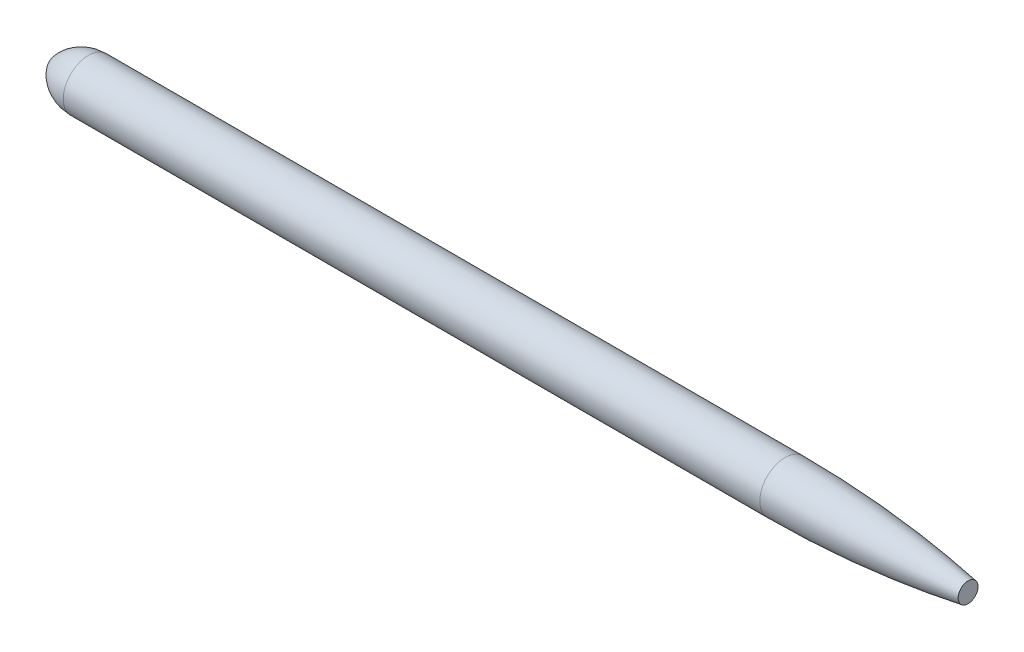
SolidWorks part; units mm, degrees
ref_plane "Front Plane" through (0, 0, 0) normal (0, 0, 1) x (1, 0, 0)
ref_plane "Top Plane" through (0, 0, 0) normal (0, 1, 0) x (1, 0, 0)
ref_plane "Right Plane" through (0, 0, 0) normal (1, 0, 0) x (0, 0, -1)
sketch "rootSketch" plane through (0, 0, 0) normal (0, 1, 0) x (1, 0, 0)
  line L0 (0, 0) -> (12000, 0) construction
  line L1 (270, -177.8) -> (270, 177.8) construction
  line L2 (0, 0) -> (6470, 0)
  line L3 (270, -177.8) -> (5180, -177.8)
  line L4 (6470, -70) -> (6470, 0)
  arc A0 (5180, -177.8) -> (6470, -70) centre (5180, 7594.5601) ccw
  arc A1 (270, -177.8) -> (0, 0) centre (270, 116.1056) cw
  point P5 (270, 0)
  dimension "rootMaxThickness" = 355.6
  dimension "D1" = 6470
  dimension "D2" = 270
  dimension "D3" = 1290
  dimension "D4" = 70
revolve "Revolve1" add sketch "rootSketch" angle 360 about L0
ref_plane "Plane1" through (5330, 0, 0) normal (1, 0, 0) x (0, 0, -1)
equation "\"length\"= 6.47"
equation "\"D1@rootSketch\" = \"length\""
equation "\"diameter\"= .3556"
equation "\"rootMaxThickness@rootSketch\"=\"diameter\""
equation "\"LEtaperlength\"= 0.27"
equation "\"TEradius\"= 0.07"
equation "\"D4@rootSketch\"=\"TEradius\""
equation "\"TEtaperlength\"= 1.29"
equation "\"D2@rootSketch\"=\"LEtaperlength\""
equation "\"D3@rootSketch\"=\"TEtaperlength\""
